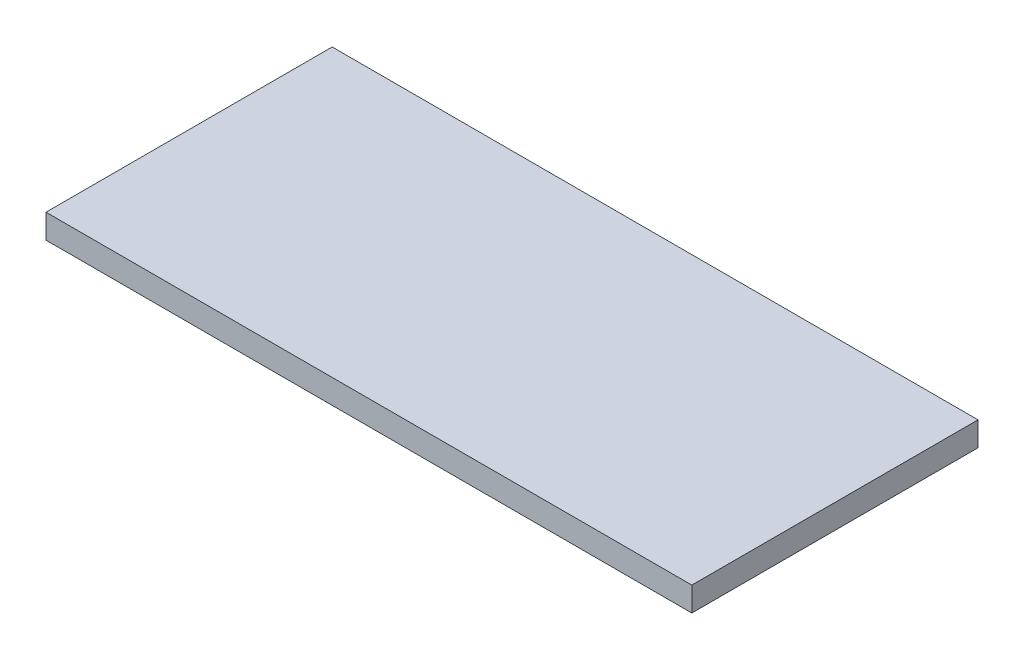
SolidWorks part; units mm, degrees
ref_plane "前视基准面" through (0, 0, 0) normal (0, 0, 1) x (1, 0, 0)
ref_plane "上视基准面" through (0, 0, 0) normal (0, 1, 0) x (1, 0, 0)
ref_plane "右视基准面" through (0, 0, 0) normal (1, 0, 0) x (0, 0, -1)
other "Configuration Table"
sketch "草图1" plane through (0, 0, 0) normal (0, 1, 0) x (1, 0, 0)
  line L1 (0, 0) -> (80, 0)
  line L2 (0, 0) -> (0, 35.45)
  line L3 (0, 35.45) -> (80, 35.45)
  line L4 (80, 0) -> (80, 35.45)
  dimension "D1" = 80
  dimension "D2" = 35.45
extrude "凸台-拉伸1" add sketch "草图1" along normal blind 3
